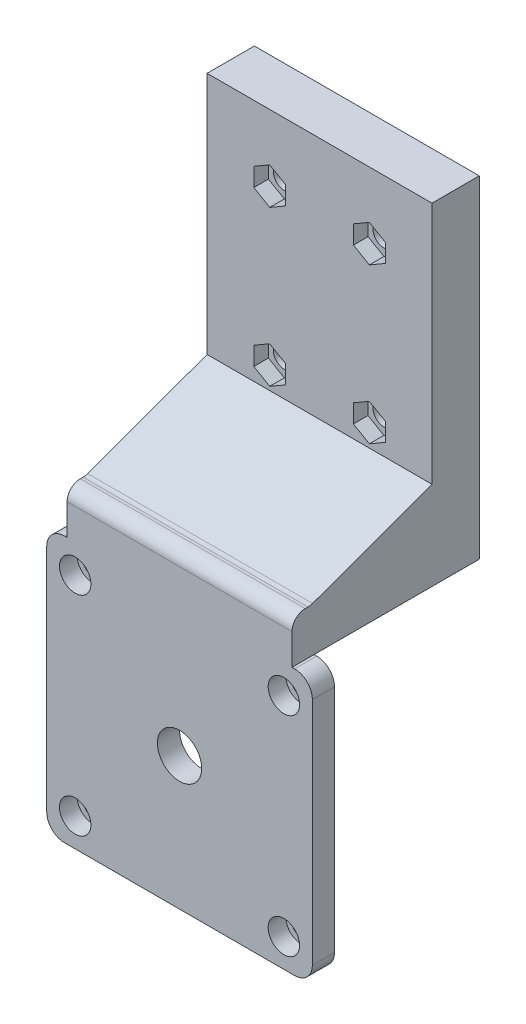
SolidWorks part; units mm, degrees
note: The reader was unsure of these and kept them because the rebuilt part matched: shared geometry of "Sketch1<3>", "Sketch1<4>", "Sketch1<5>".
ref_plane "Front Plane" through (0, 0, 0) normal (0, 0, 1) x (1, 0, 0)
ref_plane "Top Plane" through (0, 0, 0) normal (0, 1, 0) x (1, 0, 0)
ref_plane "Right Plane" through (0, 0, 0) normal (1, 0, 0) x (0, 0, -1)
sketch "Sketch1" plane through (0, 0, 0) normal (0, 0, 1) x (1, 0, 0)
  line L0 (-25.4, 60) -> (-25.4, 135)
  line L1 (-25.4, 135) -> (25.4, 135)
  line L2 (25.4, 135) -> (25.4, 60)
  line L4 (-11.25, 120) -> (11.25, 120) construction
  line L5 (-11.25, 120) -> (-11.25, 85) construction
  line L6 (-11.25, 85) -> (11.25, 85) construction
  line L7 (11.25, 120) -> (11.25, 85) construction
  line L9 (-25.4, 60) -> (25.4, 60)
  line L10 (-25.4, 70) -> (25.4, 70)
  line L11 (-23.57, 53.57) -> (23.57, 53.57) construction
  line L12 (-23.57, 53.57) -> (-23.57, 6.43) construction
  line L13 (-23.57, 6.43) -> (23.57, 6.43) construction
  line L14 (23.57, 53.57) -> (23.57, 6.43) construction
  line L16 (-26, 60) -> (26, 60)
  line L17 (-30, 56) -> (-30, 4)
  line L18 (-26, 0) -> (26, 0)
  line L19 (30, 56) -> (30, 4)
  circle A2 centre (-11.25, 120) radius 2.5
  circle A3 centre (11.25, 120) radius 2.5
  circle A4 centre (11.25, 85) radius 2.5
  circle A5 centre (-11.25, 85) radius 2.5
  circle A16 centre (-23.57, 53.57) radius 2.25
  circle A18 centre (-23.57, 6.43) radius 2.25
  circle A19 centre (23.57, 6.43) radius 2.25
  circle A20 centre (23.57, 53.57) radius 2.25
  arc A21 (26, 60) -> (30, 56) centre (26, 56) cw
  arc A22 (26, 0) -> (30, 4) centre (26, 4) ccw
  arc A23 (-30, 4) -> (-26, 0) centre (-26, 4) ccw
  arc A24 (-26, 60) -> (-30, 56) centre (-26, 56) ccw
  point P13 (0, 85)
  point P28 (0, 6.43)
  point P29 (0, 0)
  point P30 (-23.57, 30)
  point P31 (-30, 30)
  point P40 (0, 135)
  point P48 (-30, 0)
  point P51 (-30, 60)
  dimension "D4" = 5
  dimension "D10" = 4
  dimension "D13" = 4.5
  dimension "D2" = 50.8
  dimension "D5" = 35
  dimension "D7" = 22.5
  dimension "D6" = 15
  dimension "D11" = 25
  dimension "D12" = 10
  dimension "D8" = 47.14
  dimension "D9" = 60
extrude "5" add sketch "Sketch1" along normal blind 7.5 contours L0 L9 L2 L1 A5 A4 A3 A2
extrude "Boss-Extrude1" add sketch "Sketch1<3>" along normal blind 34.125 contours L10 L0 L9 L2
sketch "Sketch1<3>" plane through (0, 0, 0) normal (0, 0, 1) x (1, 0, 0) same geometry as "Sketch1"
extrude "Boss-Extrude2" add sketch "Sketch1<4>" along normal blind 5 from surface at 34.125
sketch "Sketch1<4>" plane through (0, 0, 0) normal (0, 0, 1) x (1, 0, 0) same geometry as "Sketch1"
chamfer "Chamfer1" distance 10 angle 70 1 edges at (0, 70, 7.5)
fillet "Fillet1" radius 3 2 edges at (0, 70, 39.125) (0, 70, 34.9748)
sketch "Sketch2" plane through (0, 0, 39.125) normal (0, 0, 1) x (1, 0, 0)
  line L0 (-30, 4) -> (-30, 56) construction
  circle A0 centre (0, 30) radius 5
  point P4 (-30, 30)
  dimension "D1" = 10
extrude "Cut-Extrude1" cut sketch "Sketch2" against normal through all
sketch "Sketch3" plane through (0, 0, 39.125) normal (0, 0, 1) x (1, 0, 0)
  circle A0 centre (-23.57, 53.57) radius 3.55
  circle A1 centre (23.57, 53.57) radius 3.55
  circle A2 centre (-23.57, 6.43) radius 3.55
  circle A3 centre (23.57, 6.43) radius 3.55
  circle A4 centre (23.57, 6.43) radius 2.25 construction
  circle A5 centre (-23.57, 6.43) radius 2.25 construction
  dimension "D1" = 7.1
extrude "Cut-Extrude2" cut sketch "Sketch3" against normal blind 4
sketch "Sketch4" plane through (0, 0, 7.5) normal (0, 0, 1) x (1, 0, 0)
  line L1 (-11.25, 124.1569) -> (-14.85, 122.0785)
  line L2 (-14.85, 122.0785) -> (-14.85, 117.9215)
  line L3 (-14.85, 117.9215) -> (-11.25, 115.8431)
  line L4 (-11.25, 115.8431) -> (-7.65, 117.9215)
  line L5 (-7.65, 117.9215) -> (-7.65, 122.0785)
  line L6 (-7.65, 122.0785) -> (-11.25, 124.1569)
  line L7 (11.25, 124.1569) -> (7.65, 122.0785)
  line L8 (7.65, 122.0785) -> (7.65, 117.9215)
  line L9 (7.65, 117.9215) -> (11.25, 115.8431)
  line L10 (11.25, 115.8431) -> (14.85, 117.9215)
  line L11 (14.85, 117.9215) -> (14.85, 122.0785)
  line L12 (14.85, 122.0785) -> (11.25, 124.1569)
  line L13 (-11.25, 89.1569) -> (-14.85, 87.0785)
  line L14 (-14.85, 87.0785) -> (-14.85, 82.9215)
  line L15 (-14.85, 82.9215) -> (-11.25, 80.8431)
  line L16 (-11.25, 80.8431) -> (-7.65, 82.9215)
  line L17 (-7.65, 82.9215) -> (-7.65, 87.0785)
  line L18 (-7.65, 87.0785) -> (-11.25, 89.1569)
  line L19 (11.25, 89.1569) -> (7.65, 87.0785)
  line L20 (7.65, 87.0785) -> (7.65, 82.9215)
  line L21 (7.65, 82.9215) -> (11.25, 80.8431)
  line L22 (11.25, 80.8431) -> (14.85, 82.9215)
  line L23 (14.85, 82.9215) -> (14.85, 87.0785)
  line L24 (14.85, 87.0785) -> (11.25, 89.1569)
  circle A0 centre (-11.25, 120) radius 3.6 construction
  circle A1 centre (11.25, 120) radius 3.6 construction
  circle A2 centre (-11.25, 85) radius 3.6 construction
  circle A3 centre (11.25, 85) radius 3.6 construction
  dimension "D1" = 7.2
extrude "Cut-Extrude3" cut sketch "Sketch4" against normal blind 3.3
extrude "Boss-Extrude3" add sketch "Sketch1<5>" against normal blind 3.18 contours L0 L10 L2 L1 A5 A4 A3 A2 | L10 L0 L9 L2
sketch "Sketch1<5>" plane through (0, 0, 0) normal (0, 0, 1) x (1, 0, 0) same geometry as "Sketch1"
equation "\"tube_length\"= 1.5ft"
equation "\"tube_width\"= 1in"
equation "\"tube_height\"= 2in"
equation "\"tube_thickness\"= 0.125in"
equation "\"D3@Sketch1\"=\"tube_thickness\""
equation "\"D1@Boss-Extrude1\"=\"tube_length\""
equation "\"D1@Sketch1\"=\"tube_width\""
equation "\"D2@Sketch1\"=\"tube_height\""
